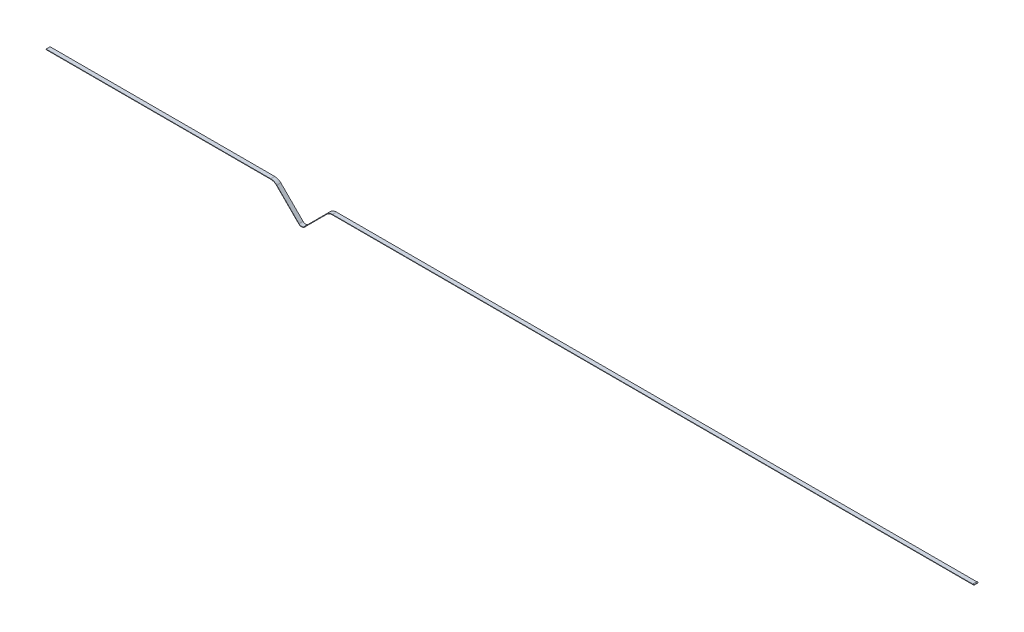
SolidWorks part; units mm, degrees
ref_plane "Front Plane" through (0, 0, 0) normal (0, 0, 1) x (1, 0, 0)
ref_plane "Top Plane" through (0, 0, 0) normal (0, 1, 0) x (1, 0, 0)
ref_plane "Right Plane" through (0, 0, 0) normal (1, 0, 0) x (0, 0, -1)
sketch "Sketch1" plane through (0, 0, 0) normal (1, 0, 0) x (0, 0, -1)
  line L1 (0, 0) -> (6, 0)
  line L2 (0, 0) -> (0, 0.63)
  line L3 (0, 0.63) -> (6, 0.63)
  line L4 (6, 0) -> (6, 0.63)
  dimension "D1" = 0.63
  dimension "D2" = 6
sketch "Sketch2" plane through (0, 0, 0) normal (0, 0, 1) x (1, 0, 0)
  line L0 (0, 0) -> (-948.2457, 0)
  line L1 (-956.7008, -3.5053) -> (-989.4926, -36.3377)
  line L2 (-998.1388, -36.3377) -> (-1030.9305, -3.5053)
  line L3 (-1039.3857, 0) -> (-1371.6, 0)
  arc A0 (-948.2457, 0) -> (-956.7008, -3.5053) centre (-948.2457, -11.95) ccw
  arc A1 (-989.4926, -36.3377) -> (-998.1388, -36.3377) centre (-993.8157, -32.02) cw
  arc A2 (-1030.9305, -3.5053) -> (-1039.3857, 0) centre (-1039.3857, -11.95) ccw
  circle A4 centre (-993.8157, -32.02) radius 6.11 construction
  circle A6 centre (-948.2457, -11.95) radius 11.95 construction
  circle A7 centre (-1039.3857, -11.95) radius 11.95 construction
  dimension "D1" = 6.11
  dimension "D4" = 1371.6
sweep "Sweep1" add profiles "Sketch1" path "Sketch2"
sketch "Sketch3" plane through (0, 0, 0) normal (0, 0, 1) x (1, 0, 0)
  line L0 (0, 0.63) -> (-948.2457, 0.63) construction
  line L1 (-1.5, 0.63) -> (-1.5, 0)
  line L2 (0, 0) -> (-948.2457, 0) construction
  line L3 (-1.5, 0) -> (0, 0)
  line L4 (0, 0) -> (0, 0.63)
  arc A1 (0, 0.63) -> (-1.5, 0.63) centre (-0.75, 0.63) ccw
  dimension "D1" = 0.75
extrude "Boss-Extrude1" add sketch "Sketch3" against normal through all
pattern_curve "CrvPattern1" [suppressed] of bodies 102 driven by "Sketch2" parameters "D1"=2000, "D3"=2, "D2"=1, "D4"=10
